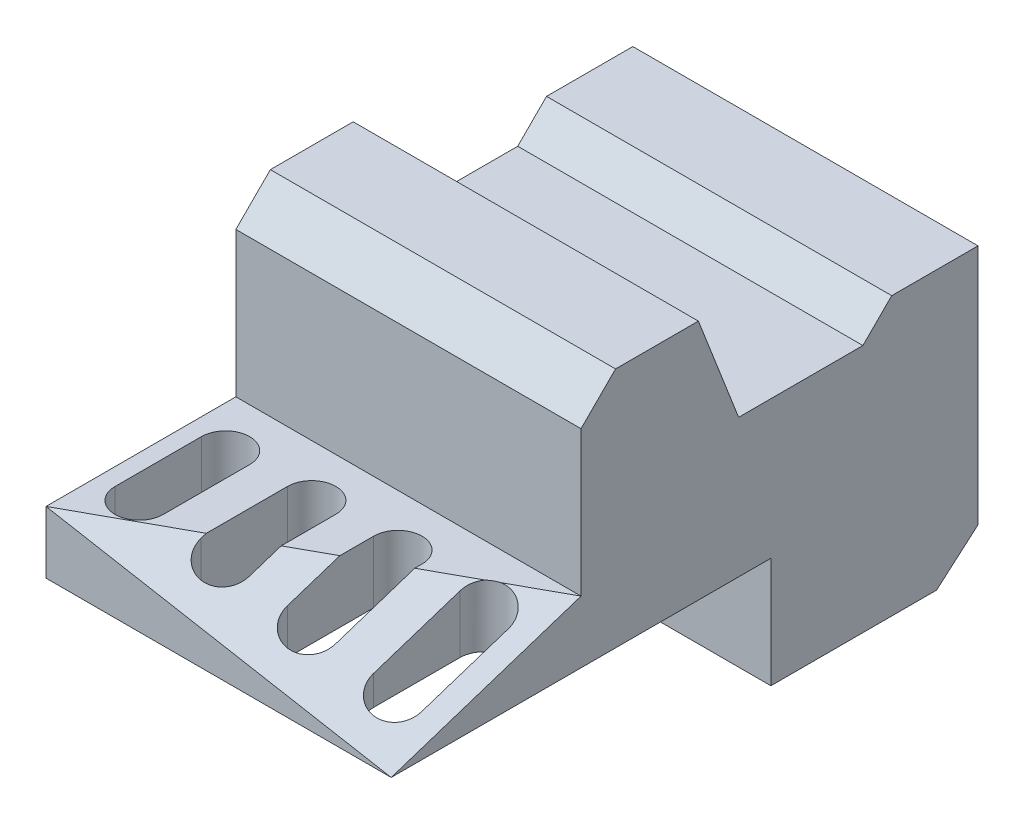
SolidWorks part; units mm, degrees
ref_plane "Plano frontal" through (0, 0, 0) normal (0, 0, 1) x (1, 0, 0)
ref_plane "Plano superior" through (0, 0, 0) normal (0, 1, 0) x (1, 0, 0)
ref_plane "Plano direito" through (0, 0, 0) normal (1, 0, 0) x (0, 0, -1)
sketch "Esboço3" plane through (0, 0, 0) normal (1, 0, 0) x (0, 0, -1)
  line L0 (0, 0) -> (0, -70)
  line L1 (0, 0) -> (-25, 0)
  line L2 (-12, -80.38) -> (-60, -80.38)
  line L3 (-25, 0) -> (-33.3439, -8.3439)
  line L4 (-33.3439, -8.3439) -> (-69.3439, -8.3439)
  line L5 (-60, -80.38) -> (-60, -48.3785)
  line L6 (-69.3439, -8.3439) -> (-81.0015, 21.62)
  line L7 (-81.0015, 21.62) -> (-105.0015, 21.62)
  line L8 (-105.0015, 21.62) -> (-115, 11.6215)
  line L9 (-115, 11.6215) -> (-115, -30.3785)
  line L10 (-115, -30.3785) -> (-170, -30.3785)
  line L11 (-170, -30.3785) -> (-170, -48.3785)
  line L12 (-170, -48.3785) -> (-60, -48.3785)
  line L13 (0, -70) -> (-12, -80.38)
  point P5 (0, -70)
  point P8 (-12, -80.38)
  dimension "D1" = 18
  dimension "D2" = 25
  dimension "D3" = 55
  dimension "D4" = 11.8
  dimension "D5" = 36
  dimension "D6" = 110
  dimension "D7" = 102
  dimension "D8" = 42
  dimension "D9" = 14.14
  dimension "D10" = 24
  dimension "D11" = 80.38
  dimension "D12" = 70
  dimension "D13" = 158
extrude "Ressalto-extrusão1" add sketch "Esboço3" along normal blind 100
sketch "Esboço5" plane through (0, -30.3785, 0) normal (0, 1, 0) x (1, 0, 0)
  line L0 (0, -142.5) -> (100, -142.5) construction
  line L1 (0, -115) -> (0, -170) construction
  line L2 (100, -115) -> (100, -170) construction
  line L3 (12, -155.02) -> (12, -129.98) construction
  line L4 (5, -155.02) -> (5, -129.98)
  line L5 (19, -155.02) -> (19, -129.98)
  line L6 (36.96, -155.02) -> (36.96, -129.98) construction
  line L7 (29.96, -155.02) -> (29.96, -129.98)
  line L8 (43.96, -155.02) -> (43.96, -129.98)
  line L9 (61.92, -155.02) -> (61.92, -129.98) construction
  line L10 (54.92, -155.02) -> (54.92, -129.98)
  line L11 (68.92, -155.02) -> (68.92, -129.98)
  line L12 (86.88, -155.02) -> (86.88, -129.98) construction
  line L13 (79.88, -155.02) -> (79.88, -129.98)
  line L14 (93.88, -155.02) -> (93.88, -129.98)
  line L15 (12, -155.02) -> (36.96, -155.02) construction
  arc A0 (5, -155.02) -> (19, -155.02) centre (12, -155.02) ccw
  arc A1 (19, -129.98) -> (5, -129.98) centre (12, -129.98) ccw
  arc A2 (29.96, -155.02) -> (43.96, -155.02) centre (36.96, -155.02) ccw
  arc A3 (43.96, -129.98) -> (29.96, -129.98) centre (36.96, -129.98) ccw
  arc A4 (54.92, -155.02) -> (68.92, -155.02) centre (61.92, -155.02) ccw
  arc A5 (68.92, -129.98) -> (54.92, -129.98) centre (61.92, -129.98) ccw
  arc A6 (79.88, -155.02) -> (93.88, -155.02) centre (86.88, -155.02) ccw
  arc A7 (93.88, -129.98) -> (79.88, -129.98) centre (86.88, -129.98) ccw
  point P8 (12, -142.5)
  point P16 (36.96, -142.5)
  point P23 (61.92, -142.5)
  point P30 (86.88, -142.5)
  dimension "D1" = 12.52
  dimension "D2" = 7
  dimension "D3" = 5
  dimension "D5" = 24.96
  dimension "D4" = 4
extrude "Corte-extrusão1" cut sketch "Esboço5" against normal through all
ref_plane "Plano1" through (3.9898, 22.1656, 7.2542) normal (0.1686, 0.9368, 0.3066) x (0.9857, -0.1603, -0.0524)
sketch "Esboço6" plane through (3.9898, 22.1656, 7.2542) normal (0.1686, 0.9368, 0.3066) x (0.9857, -0.1603, -0.0524)
  line L0 (-4.0478, -171.0164) -> (97.405, -176.6151)
  line L1 (97.405, -176.6151) -> (97.405, -118.7446)
  line L2 (97.405, -118.7446) -> (-4.0478, -171.0164)
extrude "Corte-extrusão4" cut sketch "Esboço6" along normal blind 87
sketch "Esboço9" plane through (0, 0, 0) normal (-1, 0, 0) x (0, 0, 1)
  line L0 (50, -88.5723) -> (50, 2.8812) construction
  line L1 (60, -48.3785) -> (60, -80.38) construction
  line L2 (-16.2721, -70.38) -> (105.7594, -70.38) construction
  line L3 (60, -80.38) -> (12, -80.38) construction
  line L4 (-17.7282, -41.443) -> (44.833, -95.5585) construction
  line L5 (12, -80.38) -> (0, -70) construction
  line L6 (10, 20.2742) -> (10, -95.5585) construction
  line L7 (0, -70) -> (0, 0) construction
  line L8 (20.4776, -18.3439) -> (99.5877, -18.3439) construction
  line L9 (-11.2225, -10) -> (26.9298, -10) construction
  line L10 (63.9601, 11.62) -> (128.763, 11.62) construction
  line L11 (105, 33.7397) -> (105, -60.5191) construction
  line L12 (67.607, -38.3785) -> (182.0641, -38.3785) construction
  line L13 (0, 0) -> (25, 0) construction
  line L14 (33.3439, -8.3439) -> (69.3439, -8.3439) construction
  line L15 (81.0015, 21.62) -> (105.0015, 21.62) construction
  line L16 (115, 11.6215) -> (115, -30.3785) construction
  line L17 (170, -48.3785) -> (60, -48.3785) construction
  line L18 (-8.6362, 19.4941) -> (39.6153, -28.7574) construction
  line L19 (25, 0) -> (33.3439, -8.3439) construction
  line L20 (95.4379, 31.1462) -> (72.1565, -28.6943) construction
  line L21 (69.3439, -8.3439) -> (81.0015, 21.62) construction
  line L22 (105, 11.62) -> (87.8411, 11.62)
  line L23 (87.8411, 11.62) -> (76.1835, -18.3439)
  line L24 (76.1835, -18.3439) -> (29.7819, -18.3439)
  line L25 (29.7819, -18.3439) -> (21.438, -10)
  line L26 (21.438, -10) -> (10, -10)
  line L27 (10, -10) -> (10, -65.428)
  line L28 (10, -65.428) -> (15.7249, -70.38)
  line L29 (15.7249, -70.38) -> (50, -70.38)
  line L30 (50, -70.38) -> (50, -38.3785)
  line L31 (50, -38.3785) -> (105, -38.3785)
  line L32 (105, -38.3785) -> (105, 11.62)
  dimension "D1" = 10
  dimension "D2" = 10
  dimension "D3" = 10
  dimension "D4" = 10
  dimension "D5" = 10
  dimension "D6" = 10
  dimension "D7" = 10
  dimension "D8" = 10
  dimension "D9" = 10
  dimension "D10" = 10
  dimension "D11" = 10
extrude "Corte-extrusão6" cut sketch "Esboço9" against normal blind 20
